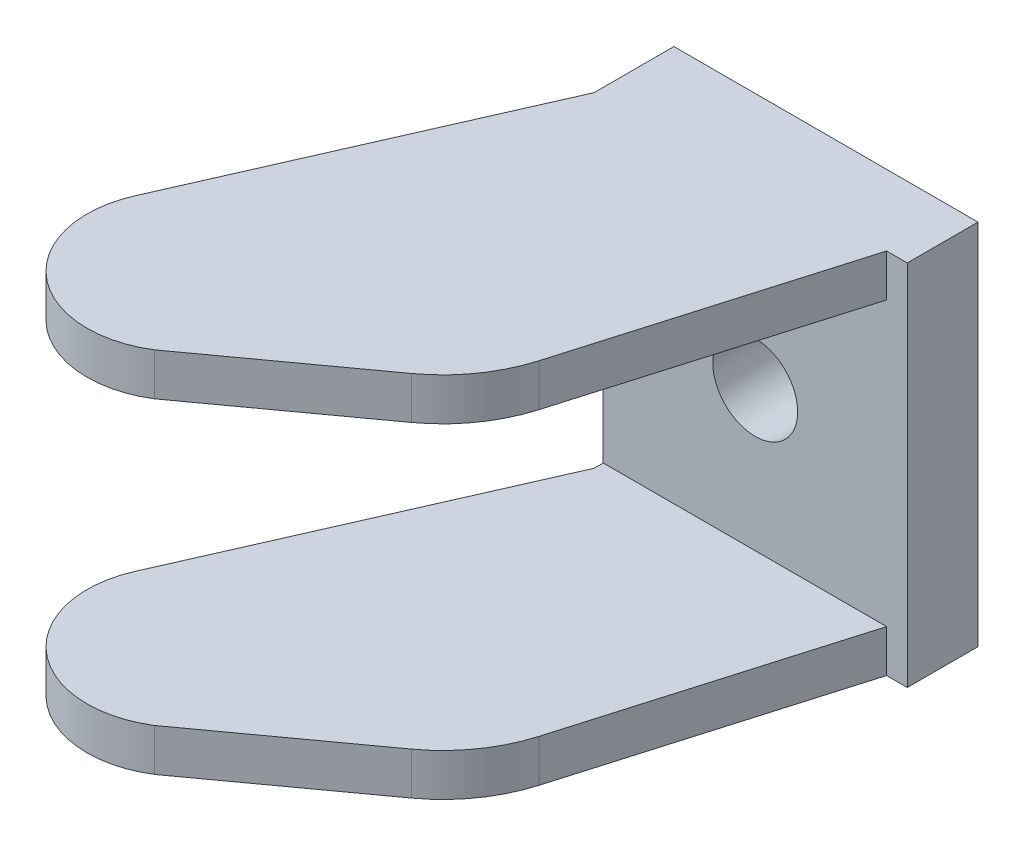
SolidWorks part; units mm, degrees
ref_plane "Front Plane" through (0, 0, 0) normal (0, 0, 1) x (1, 0, 0)
ref_plane "Top Plane" through (0, 0, 0) normal (0, 1, 0) x (1, 0, 0)
ref_plane "Right Plane" through (0, 0, 0) normal (1, 0, 0) x (0, 0, -1)
sketch "Sketch1" plane through (0, 0, 0) normal (0, 1, 0) x (1, 0, 0)
  line L0 (0, 0) -> (21.5, 0)
  line L1 (21.5, 0) -> (14.4677, -24.0129)
  line L2 (10.7419, -29.2974) -> (0.21, -36.936)
  line L3 (-9.9079, -28.1824) -> (0, -5.6494)
  line L4 (0, -5.6494) -> (0, 0)
  arc A0 (-9.9079, -28.1824) -> (0.21, -36.936) centre (-3.5, -31) ccw
  arc A1 (14.4677, -24.0129) -> (10.7419, -29.2974) centre (4.8708, -21.2024) cw
  dimension "D1" = 21.5
  dimension "D2" = 7
  dimension "D5" = 10
  dimension "D3" = 31
  dimension "D4" = 25
extrude "Boss-Extrude1" add sketch "Sketch1" along normal mid plane 26
extrude "Cut-Extrude1" cut sketch "Sketch1<2>" against normal mid plane 20
sketch "Sketch1<2>" plane through (0, 0, 0) normal (0, 1, 0) x (1, 0, 0) same geometry as "Sketch1"
sketch "Sketch4" plane through (0, 0, 0) normal (0, 0, -1) x (-1, 0, 0)
  line L1 (0, -13) -> (-21.5, -13)
  line L2 (0, -13) -> (0, 13)
  line L3 (0, 13) -> (-21.5, 13)
  line L4 (-21.5, -13) -> (-21.5, 13)
extrude "Boss-Extrude2" add sketch "Sketch4" against normal blind 5
ref_axis "Axis1" through (-3.5, 13, 31) along (0, -1, 0)
ref_point "Point1"
ref_axis "Axis2" through (10.75, 0, 0) along (0, 0, -1)
sketch "Sketch5" plane through (0, 0, 0) normal (0, 0, -1) x (-1, 0, 0)
  circle A0 centre (-10.75, 0) radius 3
extrude "Cut-Extrude2" cut sketch "Sketch5" against normal through all
